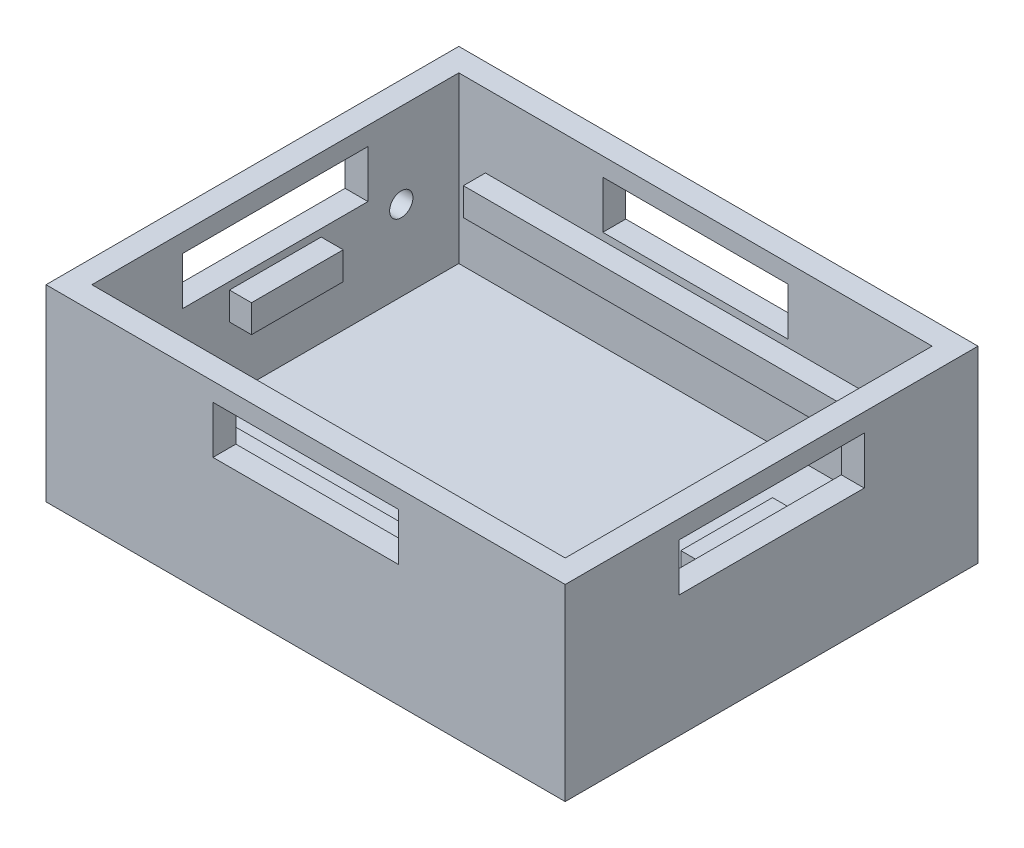
SolidWorks part; units mm, degrees
ref_plane "Front Plane" through (0, 0, 0) normal (0, 0, 1) x (1, 0, 0)
ref_plane "Top Plane" through (0, 0, 0) normal (0, 1, 0) x (1, 0, 0)
ref_plane "Right Plane" through (0, 0, 0) normal (1, 0, 0) x (0, 0, -1)
sketch "Sketch1" plane through (0, 0, 0) normal (0, 1, 0) x (1, 0, 0)
  line L0 (-2.5, 2.5) -> (-2.5, 202.5)
  line L5 (-15, -10) -> (268, -10)
  line L6 (-15, -10) -> (-15, 215)
  line L7 (-15, 215) -> (268, 215)
  line L8 (268, -10) -> (268, 215)
  line L9 (-2.5, 202.5) -> (255.5, 202.5)
  line L10 (255.5, 2.5) -> (255.5, 202.5)
  line L11 (-2.5, 2.5) -> (255.5, 2.5)
  dimension "D1" = 283
  dimension "D2" = 225
  dimension "D3" = 12.5
extrude "Walls" add sketch "Sketch1" along normal blind 90
sketch "Sketch3" plane through (0, 0, 0) normal (0, -1, 0) x (1, 0, 0)
  line L0 (268, -215) -> (-15, -215) construction
  line L1 (268, 10) -> (268, -215) construction
  line L2 (-15, 10) -> (268, 10) construction
  line L3 (-15, -215) -> (-15, 10) construction
  line L4 (268, -215) -> (-15, -215)
  line L5 (268, 10) -> (268, -215)
  line L6 (-15, 10) -> (268, 10)
  line L7 (-15, -215) -> (-15, 10)
extrude "Base" add sketch "Sketch3" along normal blind 12.5
ref_plane "Long_Support_Midplane" through (126.5, 0, 0) normal (1, 0, 0) x (0, 0, -1)
sketch "Sketch4" plane through (126.5, 0, 0) normal (1, 0, 0) x (0, 0, -1)
  line L0 (2.5, 0) -> (2.5, 90)
  line L1 (2.5, 50) -> (14.5, 50)
  line L2 (2.5, 50) -> (2.5, 34.9)
  line L3 (2.5, 34.9) -> (14.5, 34.9)
  line L4 (14.5, 50) -> (14.5, 34.9)
  line L5 (2.5, 0) -> (2.5, 90) construction
  line L6 (202.5, 50) -> (190.5, 50)
  line L7 (202.5, 50) -> (202.5, 34.9)
  line L8 (202.5, 34.9) -> (190.5, 34.9)
  line L9 (190.5, 50) -> (190.5, 34.9)
  line L14 (2.5, 0) -> (202.5, 0)
  line L15 (202.5, 0) -> (202.5, 90)
  line L16 (202.5, 90) -> (2.5, 90)
  line L17 (2.5, 90) -> (2.5, 0)
  line L18 (2.5, 0) -> (202.5, 0) construction
  line L19 (202.5, 0) -> (202.5, 90) construction
  line L20 (202.5, 90) -> (2.5, 90) construction
  line L21 (2.5, 90) -> (2.5, 0) construction
  dimension "D1" = 15.1
  dimension "D2" = 12
  dimension "D4" = 50
extrude "Long_Support" add sketch "Sketch4" along normal mid plane 229
ref_plane "Short_Support_Midplane" through (0, 0, -102.5) normal (0, 0, -1) x (-1, 0, 0)
sketch "Sketch5" plane through (0, 0, -102.5) normal (0, 0, -1) x (-1, 0, 0)
  line L1 (-255.5, 50) -> (-243.5, 50)
  line L2 (-255.5, 50) -> (-255.5, 34.9)
  line L3 (-255.5, 34.9) -> (-243.5, 34.9)
  line L4 (-243.5, 50) -> (-243.5, 34.9)
  line L5 (2.5, 50) -> (-9.5, 50)
  line L6 (2.5, 50) -> (2.5, 34.9)
  line L7 (2.5, 34.9) -> (-9.5, 34.9)
  line L8 (-9.5, 50) -> (-9.5, 34.9)
  line L12 (-255.5, 0) -> (2.5, 0)
  line L13 (2.5, 0) -> (2.5, 90)
  line L14 (2.5, 90) -> (-255.5, 90)
  line L15 (2.5, 0) -> (2.5, 90) construction
  line L16 (-255.5, 0) -> (2.5, 0) construction
  line L20 (-255.5, 90) -> (-255.5, 0)
  line L21 (-255.5, 90) -> (-255.5, 0) construction
  line L22 (2.5, 90) -> (-255.5, 90) construction
  dimension "D4" = 50
  dimension "D2" = 15.1
extrude "Short_Support" add sketch "Sketch5" along normal mid plane 50
sketch "Sketch6" plane through (-2.5, 0, 0) normal (1, 0, 0) x (0, 0, -1)
  line L4 (2.5, 0) -> (202.5, 0)
  line L5 (202.5, 0) -> (202.5, 90)
  line L6 (202.5, 90) -> (2.5, 90)
  line L7 (2.5, 90) -> (2.5, 0)
  line L8 (2.5, 0) -> (202.5, 0) construction
  line L9 (202.5, 0) -> (202.5, 90) construction
  line L10 (202.5, 90) -> (2.5, 90) construction
  line L11 (2.5, 90) -> (2.5, 0) construction
  circle A0 centre (171.15, 43.65) radius 6.35
  dimension "D2" = 12.7
  dimension "D3" = 31.35
  dimension "D4" = 43.65
extrude "Cut-Extrude4" cut sketch "Sketch6" against normal up to next
sketch "Sketch7" plane through (-2.5, 0, 0) normal (1, 0, 0) x (0, 0, -1)
  line L0 (127.5, 50) -> (77.5, 50) construction
  line L1 (52, 54) -> (153, 54)
  line L2 (52, 54) -> (52, 80)
  line L3 (52, 80) -> (153, 80)
  line L4 (153, 54) -> (153, 80)
  line L5 (202.5, 90) -> (2.5, 90) construction
  line L7 (102.5, 80) -> (102.5, 54) construction
  line L8 (102.5, -27.5) -> (102.5, 27.5) construction
  dimension "D1" = 4
  dimension "D2" = 10
  dimension "D3" = 26
  dimension "D4" = 101
extrude "Cut-Extrude5" cut sketch "Sketch7" against normal up to surface (12.5 mm away) up to face at (-15, 43.65, -177.5)
pattern_linear "LPattern1" count 2 spacing 270.5 along (1, 0, 0) of "Cut-Extrude5"
sketch "Sketch8" plane through (0, 0, -2.5) normal (0, 0, 1) x (1, 0, 0)
  line L1 (76, 54) -> (177, 54)
  line L2 (76, 54) -> (76, 80)
  line L3 (76, 80) -> (177, 80)
  line L4 (177, 54) -> (177, 80)
  line L6 (241, 50) -> (12, 50) construction
  line L7 (126.5, 80) -> (126.5, 54) construction
  line L9 (-2.5, 90) -> (255.5, 90) construction
  line L10 (126.5, -28.05) -> (126.5, 28.05) construction
  dimension "D3" = 26
  dimension "D4" = 101
  dimension "D1" = 4
  dimension "D2" = 10
extrude "Cut-Extrude6" cut sketch "Sketch8" along normal up to surface (12.5 mm away) contours L4 L3 L2 L1 up to face at (126.5, 38.75, 10)
pattern_linear "LPattern2" count 2 spacing 212.5 along (0, 0, -1) of "Cut-Extrude6"
equation "\"Length\"= 283"
equation "\"Width\"= 225"
equation "\"WallThickness\"= 12.5"
equation "\"UpperWaterJacketThickness\"= 28"
equation "\"SpacerHeight\"= 80.2"
equation "\"PlateLength\"=252"
equation "\"PlateWidth\"=190"
equation "\"PlateHoleDiameter\"=5.9"
equation "\"PlateHoleBottom\"= 2"
equation "\"PlateHoleSide\"= 1.55"
equation "\"PlateHoleSpacing\"= 3.1"
equation "\"PlateThickness\"=1.55"
equation "\"D1@Sketch1\"=\"Length\""
equation "\"D2@Sketch1\"=\"Width\""
equation "\"D3@Sketch1\"=\"WallThickness\""
equation "\"ReservoirBottom\"=12.5"
equation "\"D1@Base\"=\"ReservoirBottom\""
equation "\"ReservoirSupportWidth\"=12"
equation "\"D2@Sketch4\"=\"ReservoirSupportWidth\""
equation "\"ReservoirSupportHeight\"=15.1"
equation "\"D1@Sketch4\"=\"ReservoirSupportHeight\""
equation "\"D1@Sketch5\"=\"ReservoirSupportWidth\""
equation "\"D2@Sketch5\"=\"ReservoirSupportHeight\""
equation "\"ReservoirSupportPlacementHeight\"=50"
equation "\"D4@Sketch5\"=\"ReservoirSupportPlacementHeight\""
equation "\"D4@Sketch4\"=\"ReservoirSupportPlacementHeight\""
equation "\"ReservoirHoleDiameter\"=12.7"
equation "\"D2@Sketch6\"=\"ReservoirHoleDiameter\""
equation "\"ReservoirHoleRight\"= 25"
equation "\"D3@Sketch6\"=\"ReservoirHoleRight\"+\"ReservoirHoleDiameter\"/2"
equation "\"ReservoirHoleTop\"= \"ReservoirSupportPlacementHeight\""
equation "\"D4@Sketch6\"=\"ReservoirHoleTop\"-\"ReservoirHoleDiameter\"/2"
equation "\"ReservoirHeight\"=90"
equation "\"D1@Walls\"=\"ReservoirHeight\""
equation "\"ReservoirPortBottom\"=4"
equation "\"D1@Sketch7\"=\"ReservoirPortBottom\""
equation "\"ReservoirPortTop\"= 10"
equation "\"D2@Sketch7\"=\"ReservoirPortTop\""
equation "\"ReservoirPortWidth\"=101"
equation "\"D4@Sketch7\"=\"ReservoirPortWidth\""
equation "\"D4@Sketch8\"=\"ReservoirPortWidth\""
equation "\"D1@Sketch8\"=\"ReservoirPortBottom\""
equation "\"D2@Sketch8\"=\"ReservoirPortTop\""
